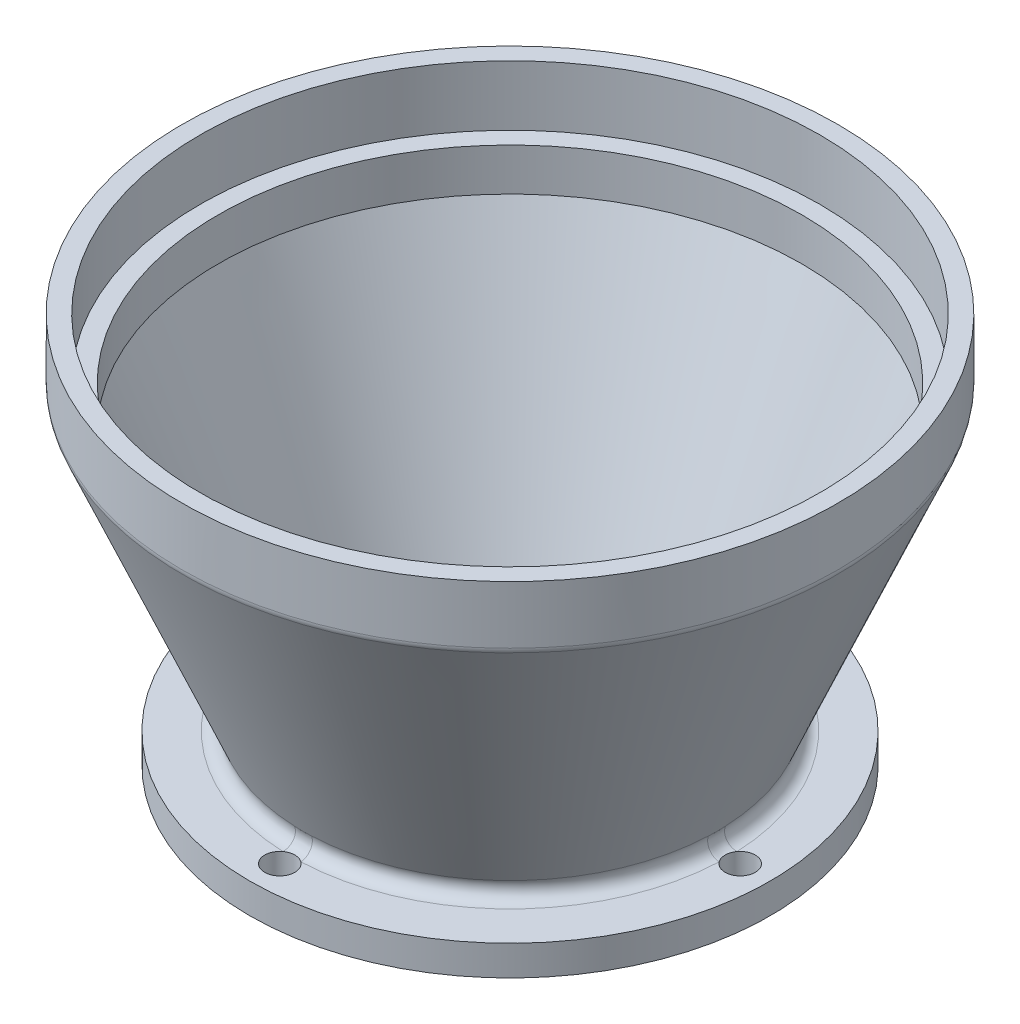
SolidWorks part; units mm, degrees
ref_plane "Front Plane" through (0, 0, 0) normal (0, 0, 1) x (1, 0, 0)
ref_plane "Top Plane" through (0, 0, 0) normal (0, 1, 0) x (1, 0, 0)
ref_plane "Right Plane" through (0, 0, 0) normal (1, 0, 0) x (0, 0, -1)
sketch "Sketch2" plane through (0, 0, 0) normal (0, 0, 1) x (1, 0, 0)
  line L0 (30.25, 0) -> (43.25, 0)
  line L1 (43.25, 0) -> (43.25, 5)
  line L2 (43.25, 5) -> (30.25, 5)
  line L3 (51.5, 55) -> (54.5, 55)
  line L10 (33.25, 5) -> (54.5, 55)
  line L11 (51.5, 55) -> (30.25, 5)
  line L12 (54.5, 55) -> (54.5, 65)
  line L13 (51.5, 55) -> (48.5, 55)
  line L14 (48.5, 55) -> (48.5, 47.9412)
  line L15 (54.5, 65) -> (51.5, 65)
  line L16 (51.5, 55) -> (51.5, 65)
  line L17 (30.25, 5) -> (30.25, 0)
  line L18 (0, 0) -> (0, 115) construction
  dimension "D1" = 43.25
  dimension "D2" = 5
  dimension "D3" = 3
  dimension "D4" = 3
  dimension "D5" = 10
  dimension "D7" = 51.5
  dimension "D8" = 10
  dimension "D9" = 50
  dimension "D10" = 3
revolve "Revolve1" add sketch "Sketch2" angle 360 about L18 region at (36.75, 2.5, 0) region at (42.375, 30, 0) region at (49.5, 52.6471, 0) region at (53, 60, 0)
sketch "Sketch3" plane through (0, 0, 0) normal (0, -1, 0) x (-1, 0, 0)
  circle A0 centre (0, 0) radius 38.25 construction
  circle A1 centre (0, 0) radius 43.25 construction
  circle A2 centre (0, -38.25) radius 2.5
  circle A3 centre (-38.25, 0) radius 2.5
  circle A4 centre (0, 38.25) radius 2.5
  circle A5 centre (38.25, 0) radius 2.5
  dimension "D1" = 5
  dimension "D2" = 5
  dimension "D3" = 5
  dimension "D4" = 5
  dimension "D5" = 5
extrude "Cut-Extrude1" cut sketch "Sketch3" against normal blind 5 contours A2 | A3 | A4 | A5
fillet "Fillet1" radius 2 2 edges at (0, 55, -54.5) (0, 5, -33.25)
